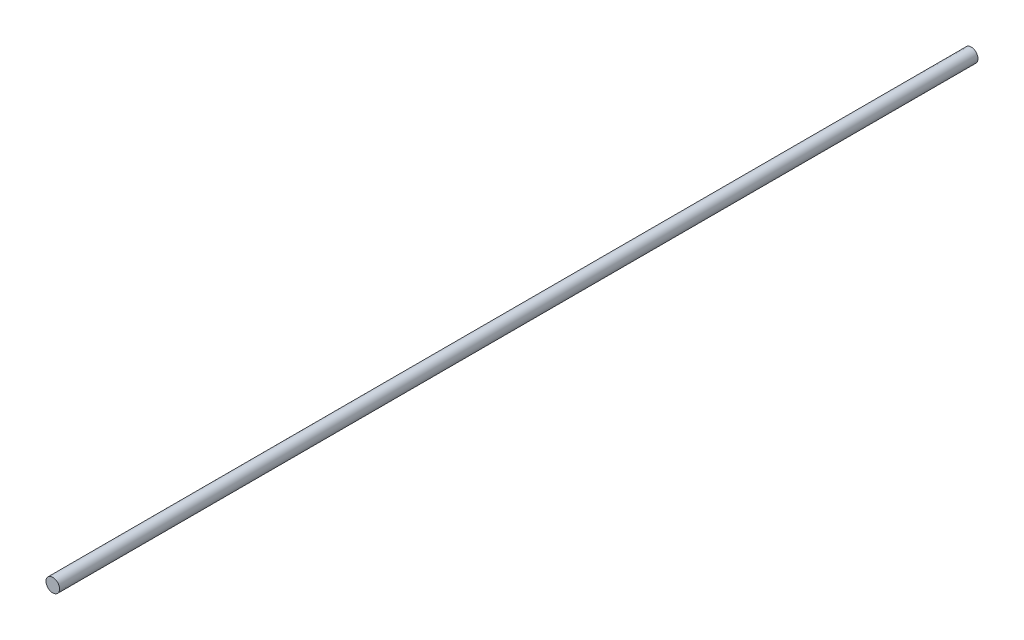
SolidWorks part; units mm, degrees
ref_plane "Plan de face" through (0, 0, 0) normal (0, 0, 1) x (1, 0, 0)
ref_plane "Plan de dessus" through (0, 0, 0) normal (0, 1, 0) x (1, 0, 0)
ref_plane "Plan de droite" through (0, 0, 0) normal (1, 0, 0) x (0, 0, -1)
sketch "Esquisse1" plane through (0, 0, 0) normal (0, 0, 1) x (1, 0, 0)
  circle A0 centre (0, 0) radius 2.105
  dimension "D1" = 4.21
extrude "Boss.-Extru.1" add sketch "Esquisse1" along normal blind 285
